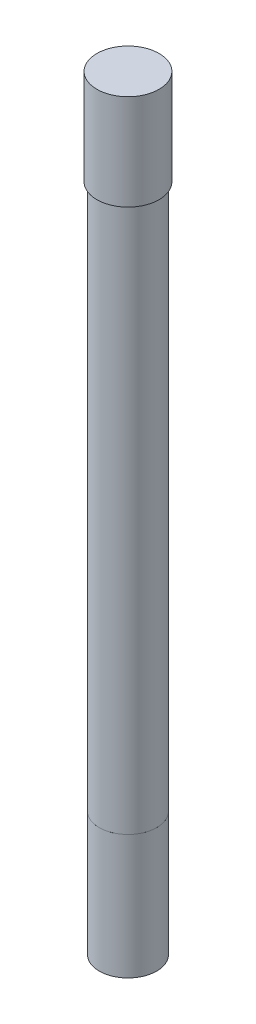
SolidWorks part; units mm, degrees
ref_plane "Front Plane" through (0, 0, 0) normal (0, 0, 1) x (1, 0, 0)
ref_plane "Top Plane" through (0, 0, 0) normal (0, 1, 0) x (1, 0, 0)
ref_plane "Right Plane" through (0, 0, 0) normal (1, 0, 0) x (0, 0, -1)
sketch "SK Bulb guard" plane through (0, 0, 0) normal (0, 1, 0) x (1, 0, 0)
  circle A0 centre (0, 0) radius 6
extrude "Bulb guard" add sketch "SK Bulb guard" along normal blind 26 separate body
sketch "SK Electrode body" plane through (0, 0, 0) normal (0, 1, 0) x (1, 0, 0)
  circle A0 centre (0, 0) radius 6
extrude "Electrode body" add sketch "SK Electrode body" along normal blind 114 from offset 26 separate body
sketch "SK Electrode cap" plane through (0, 0, 0) normal (0, 1, 0) x (1, 0, 0)
  circle A0 centre (0, 0) radius 6.5
extrude "Electrode cap" add sketch "SK Electrode cap" along normal blind 20 from offset 140 separate body
sketch "SK Cable" plane through (0, 0, 0) normal (0, 1, 0) x (1, 0, 0)
  circle A0 centre (0, 0) radius 2.2
extrude "Cable" [suppressed] add sketch "SK Cable" along normal blind 40 from offset 160 separate body
